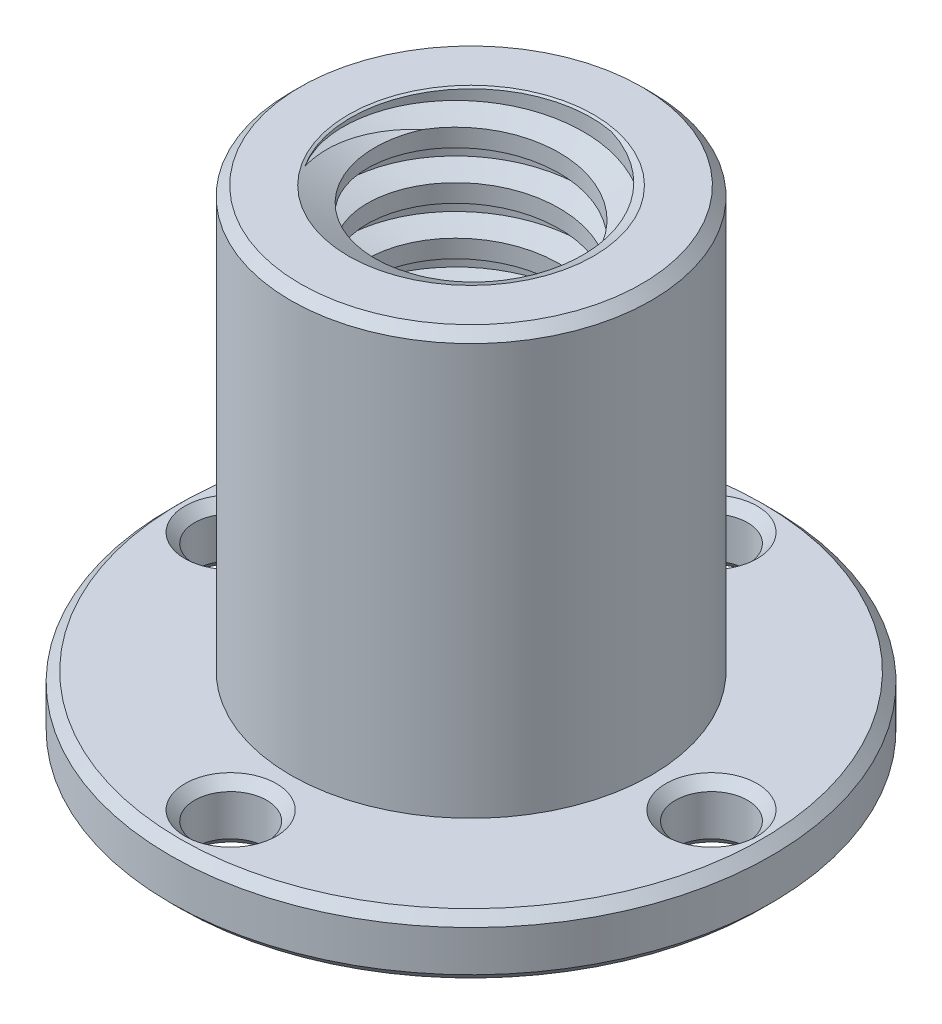
SolidWorks part; units mm, degrees
material "Phosphor bronze 10% D, UNS C52400"
ref_plane "Front Plane" through (0, 0, 0) normal (0, 0, 1) x (1, 0, 0)
ref_plane "Top Plane" through (0, 0, 0) normal (0, 1, 0) x (1, 0, 0)
ref_plane "Right Plane" through (0, 0, 0) normal (1, 0, 0) x (0, 0, -1)
sketch "Sketch1" plane through (0, 0, 0) normal (0, 1, 0) x (1, 0, 0)
  circle A0 centre (0, 0) radius 15.875
  circle A1 centre (0, 0) radius 9.525 construction
  circle A2 centre (0, 0) radius 6.35 construction
  dimension "D1" = 19.05
  dimension "OD" = 31.75
  dimension "Thread OD" = 12.7
extrude "Boss-Extrude1" add sketch "Sketch1" along normal blind 25.4
sketch "Sketch2" plane through (0, 25.4, 0) normal (0, 1, 0) x (1, 0, 0)
  circle A0 centre (0, 0) radius 6.35 construction
  circle A1 centre (0, 0) radius 6.35
extrude "Cut-Extrude1" cut sketch "Sketch2" against normal up to next
sketch "Sketch3" plane through (0, 25.4, 0) normal (0, 1, 0) x (1, 0, 0)
  circle A1 centre (0, 0) radius 6.35
  circle A2 centre (0, 0) radius 6.35
  point P0 (0, 6.35)
  dimension "D1" = 0
curve "Helix/Spiral1" pitch 2.54 height 27.94 turns 11 parameters "Pitch"=2.54
sketch "Sketch4" plane through (0, 0, 0) normal (1, 0, 0) x (0, 0, -1)
  line L0 (6.35, 26.9984) -> (5.08, 26.67)
  line L1 (5.08, 26.67) -> (5.08, 25.7284)
  line L2 (5.08, 25.7284) -> (6.35, 25.4)
  line L3 (6.35, 25.4) -> (6.35, 26.9984)
  line L4 (5.715, 26.8342) -> (5.715, 25.5642) construction
  line L7 (5.08, 26.1992) -> (6.35, 26.1992) construction
  line L8 (6.35, 25.4) -> (6.35, 24.4584) construction
  dimension "a" = 14.5
  dimension "2A" = 29
  dimension "p" = 2.54
  dimension "t" = 1.27
  dimension "h" = 1.27
sweep "Sweep1" add profiles "Sketch4" path "Helix/Spiral1"
sketch "Sketch5" plane through (0, 25.4, 0) normal (0, 1, 0) x (1, 0, 0)
  line L0 (-4.5799, 4.5799) -> (0, 0) construction
  line L1 (0, 0) -> (0, 6.477) construction
  circle A0 centre (0, 0) radius 6.35 construction
  circle A1 centre (0, 0) radius 6.477
  dimension "D2" = 45
  dimension "D1" = 0.127
extrude "Cut-Extrude3" cut sketch "Sketch5" against normal through all draft 60 and the other way through all draft 60
sketch "Sketch6" plane through (0, 0, 0) normal (0, -1, 0) x (1, 0, 0)
  circle A1 centre (0, 0) radius 6.477
  circle A2 centre (0, 0) radius 6.477
  dimension "D1" = 0
extrude "Cut-Extrude4" cut sketch "Sketch6" against normal through all draft 60 and the other way through all draft 60
sketch "Sketch7" plane through (0, 25.4, 0) normal (0, 1, 0) x (1, 0, 0)
  circle A0 centre (0, 0) radius 9.525 construction
  circle A2 centre (0, 0) radius 9.525
extrude "Cut-Extrude5" cut sketch "Sketch7" against normal offset from surface (22.225 mm away) 3.175 flip side to cut up to face at (0, 0, 6.477)
sketch "Sketch8" plane through (0, 3.175, 0) normal (0, 1, 0) x (1, 0, 0)
  circle A0 centre (-12.7, 0) radius 1.905
  circle A1 centre (0, 12.7) radius 1.905
  circle A2 centre (12.7, 0) radius 1.905
  circle A3 centre (0, -12.7) radius 1.905
  circle A4 centre (0, 0) radius 12.7 construction
  dimension "D1" = 3.81
  dimension "D2" = 25.4
extrude "Cut-Extrude6" cut sketch "Sketch8" against normal through all
chamfer "Chamfer1" distance 0.508 angle 45 11 edges at (12.7, 0, 1.905) (12.7, 3.175, 1.905) (0, 0, 14.605) (0, 3.175, 14.605) (0, 0, -10.795) (0, 3.175, -10.795) (-12.7, 0, 1.905) (-12.7, 3.175, 1.905) (0, 3.175, 15.875) (0, 0, 15.875) (0, 25.4, 9.525)
equation "\"D3@Helix/Spiral1\" = \"Pitch@Helix/Spiral1\" + \"Ht.@Boss-Extrude1\""
equation "\"p@Sketch4\" = \"Pitch@Helix/Spiral1\""
equation "\"h@Sketch4\" = \"p@Sketch4\" / 2"
equation "\"t@Sketch4\" = \"p@Sketch4\" / 2"
equation "\"D1@Sketch5\" = \"Pitch@Helix/Spiral1\" * 0.05"
